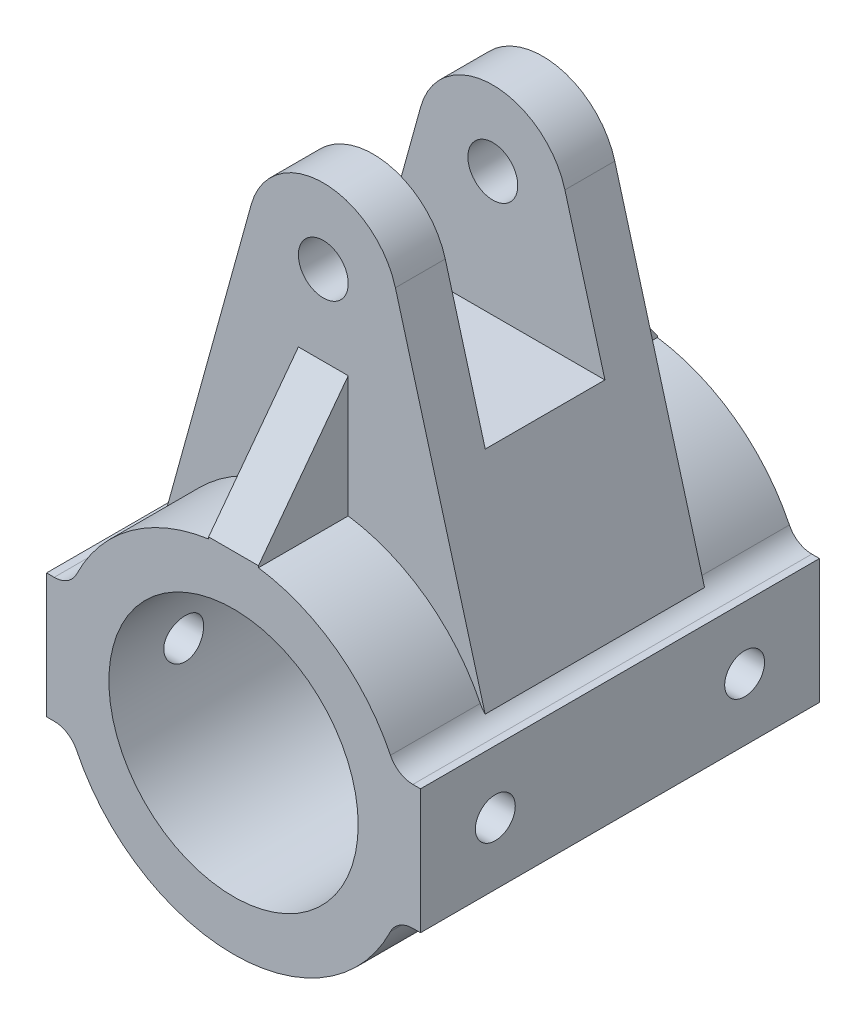
SolidWorks part; units mm, degrees
ref_plane "Front Plane" through (0, 0, 0) normal (0, 0, 1) x (1, 0, 0)
ref_plane "Top Plane" through (0, 0, 0) normal (0, 1, 0) x (1, 0, 0)
ref_plane "Right Plane" through (0, 0, 0) normal (1, 0, 0) x (0, 0, -1)
sketch "Sketch1" plane through (0, 0, 0) normal (0, 0, 1) x (1, 0, 0)
  circle A0 centre (0, 0) radius 35
  dimension "D1" = 70
extrude "Boss-Extrude1" add sketch "Sketch1" along normal mid plane 80
sketch "Sketch2" plane through (0, 0, 0) normal (0, 0, 1) x (1, 0, 0)
  line L0 (-33.7326, 9.3333) -> (-14.4568, 79)
  line L1 (33.7326, 9.3333) -> (14.4568, 79)
  arc A0 (14.4568, 79) -> (-14.4568, 79) centre (0, 75) ccw
  circle A1 centre (0, 0) radius 35 construction
  arc A2 (33.7326, 9.3333) -> (-33.7326, 9.3333) centre (0, 0) ccw
  circle A3 centre (0, 75) radius 5
  dimension "D1" = 30
  dimension "D3" = 10
  dimension "D2" = 75
extrude "Boss-Extrude2" add sketch "Sketch2" along normal mid plane 44
sketch "Sketch3" plane through (0, 0, 0) normal (1, 0, 0) x (0, 0, -1)
  line L0 (-40, 35) -> (-22, 59)
  line L1 (-22, 9.3333) -> (-22, 79) construction
  line L2 (-40, 35) -> (-40, 0)
  line L3 (-40, 35) -> (-40, -35) construction
  line L4 (-40, 0) -> (40, 0)
  line L5 (40, -35) -> (40, 35) construction
  line L6 (40, 0) -> (40, 35)
  line L7 (0, 38.5) -> (0, -38.5) construction
  line L8 (40, 35) -> (22, 59)
  line L9 (-22, 59) -> (22, 59)
  dimension "D1" = 59
extrude "Boss-Extrude3" add sketch "Sketch3" along normal mid plane 10
hole_wizard "Hole1" positions "Sketch4" profile "Sketch5" legacy end condition through all
sketch "Sketch4" plane through (0, 0, 40) normal (0, 0, 1) x (1, 0, 0)
  point P0 (0, 0)
sketch "Sketch5" plane through (0, 0, 40) normal (1, 0, 0) x (0, -1, 0)
  line L0 (0, 0) -> (0, 80)
  line L1 (0, 80) -> (25, 80)
  line L2 (25, 80) -> (25, 0)
  line L3 (25, 0) -> (0, 0)
  line L4 (0, 110) -> (0, -10) construction
  dimension "Diameter" = 50
  dimension "Depth" = 80
sketch "Sketch6" plane through (0, 0, 40) normal (0, 0, 1) x (1, 0, 0)
  line L0 (0, 0) -> (42.9559, 0) construction
  line L1 (-37.5, 12.5) -> (37.5, 12.5)
  line L2 (-37.5, 12.5) -> (-37.5, -12.5)
  line L3 (-37.5, -12.5) -> (37.5, -12.5)
  line L4 (37.5, 12.5) -> (37.5, -12.5)
  line L5 (0, 0) -> (0, 21.6886) construction
  arc A0 (-5, 34.641) -> (5, 34.641) centre (0, 0) ccw construction
  circle A1 centre (0, 0) radius 25 construction
  arc A2 (-5, 34.641) -> (5, 34.641) centre (0, 0) ccw
  circle A3 centre (0, 0) radius 25
  dimension "D1" = 25
  dimension "D2" = 75
sketch "Sketch7" plane through (0, 0, 0) normal (0, 0, 1) x (1, 0, 0)
  line L0 (37.5, 12.5) -> (37.5, -12.5) construction
  line L1 (-37.5, -12.5) -> (37.5, -12.5) construction
  line L2 (-37.5, 12.5) -> (-37.5, -12.5) construction
  line L3 (-37.5, 12.5) -> (37.5, 12.5) construction
  line L4 (37.5, 12.5) -> (37.5, -12.5)
  line L5 (-37.5, -12.5) -> (37.5, -12.5)
  line L6 (-37.5, 12.5) -> (-37.5, -12.5)
  line L7 (-37.5, 12.5) -> (37.5, 12.5)
extrude "Boss-Extrude4" add sketch "Sketch7" against normal up to surface and the other way up to surface up to face at (25, 0, -40) other way up to face at (25, 0, 40)
hole_wizard "Hole2" positions "Sketch8" profile "Sketch9" legacy end condition through all
sketch "Sketch8" plane through (0, 0, 40) normal (0, 0, 1) x (1, 0, 0)
  point P0 (0, 0)
sketch "Sketch9" plane through (0, 0, 40) normal (1, 0, 0) x (0, -1, 0)
  line L0 (0, 0) -> (0, 80)
  line L1 (0, 80) -> (25, 80)
  line L2 (25, 80) -> (25, 0)
  line L3 (25, 0) -> (0, 0)
  line L4 (0, 110) -> (0, -10) construction
  dimension "Diameter" = 50
  dimension "Depth" = 80
sketch "Sketch11" plane through (0, 0, 0) normal (1, 0, 0) x (0, 0, -1)
  line L0 (0, 0) -> (0, 116.0551) construction
  line L1 (22, 90) -> (-22, 90) construction
  line L2 (-12, 90) -> (12, 90)
  line L3 (-12, 90) -> (-12, 50)
  line L4 (-12, 50) -> (12, 50)
  line L5 (12, 90) -> (12, 50)
  line L6 (-22, 90) -> (-22, 79) construction
  dimension "D1" = 10
  dimension "D2" = 40
extrude "Cut-Extrude1" cut sketch "Sketch11" against normal through all both and the other way through all
hole_wizard "Hole3" positions "Sketch12" profile "Sketch13" legacy end condition through all
sketch "Sketch12" plane through (37.5, 0, 0) normal (1, 0, 0) x (0, 0, -1)
  point P0 (-25, 0)
  point P2 (25, 0)
  point P8 (0, 0)
  point P9 (0, 0)
  point P10 (-134.8442, 63.8535)
  dimension "D1" = 50
  dimension "D2" = 25
sketch "Sketch13" plane through (37.5, 0, 25) normal (0, 1, 0) x (0, 0, -1)
  line L0 (0, 0) -> (0, 75)
  line L1 (0, 75) -> (4, 75)
  line L2 (4, 75) -> (4, 0)
  line L3 (4, 0) -> (0, 0)
  line L4 (0, 110) -> (0, -10) construction
  dimension "Diameter" = 8
  dimension "Depth" = 75
fillet "Fillet1" radius 5 4 edges at (32.6917, -12.5, 0) (-32.6917, -12.5, 0) (-32.6917, 12.5, 31) (32.6917, 12.5, 31)
